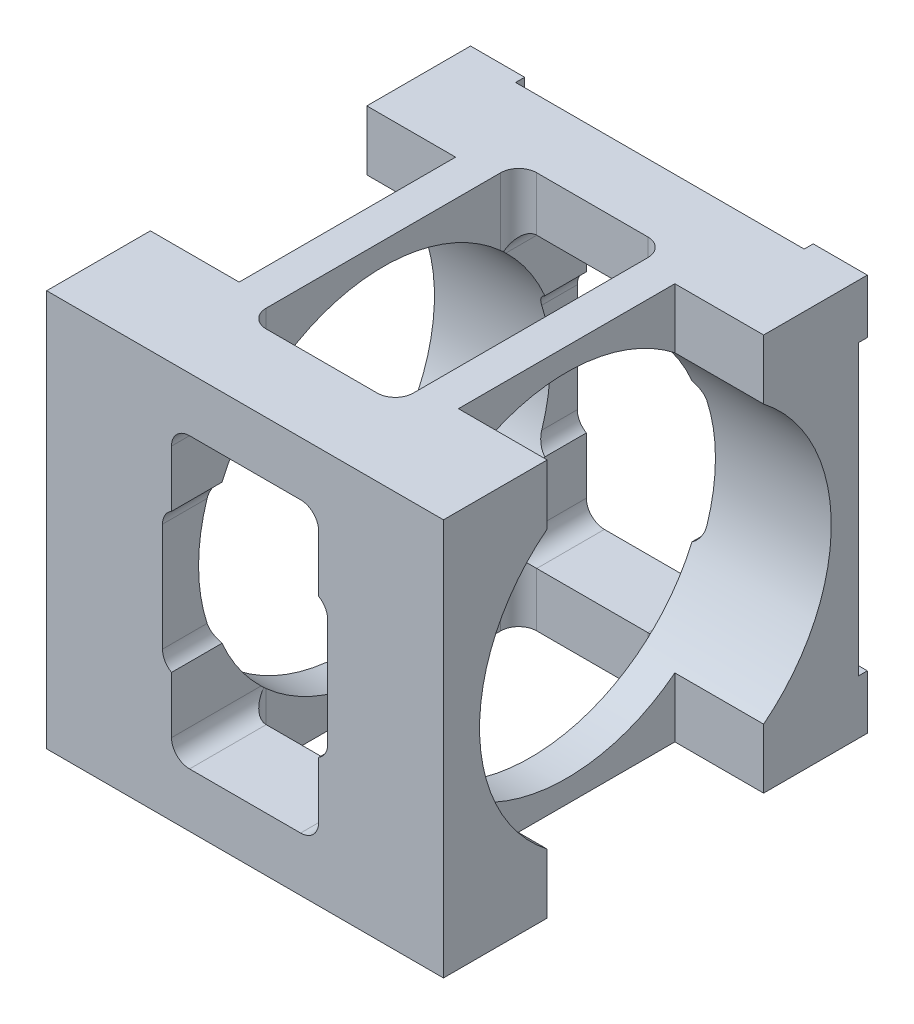
SolidWorks part; units mm, degrees
material "1060 Alloy"
ref_plane "Front Plane" through (0, 0, 0) normal (0, 0, 1) x (1, 0, 0)
ref_plane "Top Plane" through (0, 0, 0) normal (0, 1, 0) x (1, 0, 0)
ref_plane "Right Plane" through (0, 0, 0) normal (1, 0, 0) x (0, 0, -1)
sketch "Sketch1" plane through (0, 0, 0) normal (0, 0, 1) x (1, 0, 0)
  line L0 (0, 70) -> (0, 0) construction
  line L1 (12.5, 70) -> (-12.5, 70) construction
  line L2 (-12.5, 70) -> (-12.5, 0) construction
  line L3 (-11, 40) -> (11, 40)
  line L4 (-11, 40) -> (-11, 62)
  line L5 (-11, 62) -> (11, 62)
  line L6 (11, 40) -> (11, 62)
  line L7 (-11, 40) -> (11, 62) construction
  line L8 (-11, 62) -> (11, 40) construction
  point P5 (0, 51)
  dimension "D1" = 1.5
  dimension "D2" = 8
extrude "Boss-Extrude1" add sketch "Sketch1" along normal offset from surface (23.5 mm away) 1.5
sketch "Sketch2" plane through (11, 0, 0) normal (1, 0, 0) x (0, 0, -1)
  line L1 (-23.5, 51) -> (0, 51) construction
  line L2 (-23.5, 62) -> (-23.5, 40) construction
  line L3 (0, 40) -> (0, 62) construction
  circle A0 centre (-11.75, 51) radius 9.75
  dimension "D1" = 19.5
extrude "Cut-Extrude1" cut sketch "Sketch2" against normal up to next
sketch "Sketch3" plane through (0, 0, 0) normal (0, 0, -1) x (-1, 0, 0)
  line L0 (0, 62) -> (0, 40) construction
  line L1 (-11, 62) -> (11, 62) construction
  line L2 (11, 40) -> (-11, 40) construction
  line L3 (-11, 51) -> (11, 51) construction
  line L4 (-11, 40) -> (-11, 62) construction
  line L5 (11, 62) -> (11, 40) construction
  line L6 (11, 59) -> (8, 59)
  line L7 (-11, 62) -> (-8, 62)
  line L8 (-11, 62) -> (-11, 59)
  line L9 (-11, 59) -> (-8, 59)
  line L10 (-8, 62) -> (-8, 59)
  line L11 (8, 62) -> (8, 59)
  line L12 (11, 62) -> (8, 62)
  line L13 (11, 62) -> (11, 59)
  line L14 (11, 40) -> (11, 43)
  line L15 (11, 40) -> (8, 40)
  line L16 (8, 40) -> (8, 43)
  line L17 (-8, 40) -> (-8, 43)
  line L18 (-11, 43) -> (-8, 43)
  line L19 (-11, 40) -> (-11, 43)
  line L20 (-11, 40) -> (-8, 40)
  line L21 (11, 43) -> (8, 43)
  line M1 (-11, 62) -> (-11, 40)
  line M2 (-11, 40) -> (11, 40)
  line M3 (11, 40) -> (11, 62)
  line M4 (11, 62) -> (-11, 62)
  dimension "D1" = 3
extrude "Cut-Extrude2" cut sketch "Sketch3" against normal blind 0.5 contours L21 L6 L11 L10 L9 L18 L17 L16 M3 M4 M1 M2
sketch3d "3DSketch1"
  line L0 (-11, 51, 23.5) -> (11, 51, 23.5) construction
  line L4 (-11, 40, 23.5) -> (-11, 62, 23.5) construction
  line L5 (11, 62, 23.5) -> (11, 40, 23.5) construction
  line L6 (0, 51, 23.5) -> (0, 51, 0.5) construction
  point P0 (0, 51, 23.5)
sketch "Sketch5" plane through (0, 0, 23.5) normal (0, 0, 1) x (1, 0, 0)
  line L0 (0, 40) -> (0, 62) construction
  line L1 (11, 40) -> (-11, 40) construction
  line L2 (-11, 62) -> (11, 62) construction
  line L3 (3.8786, 43.5) -> (3.8786, 58.5) construction
  line L4 (-4.0786, 43) -> (4.0786, 43)
  line L5 (-4.0786, 43) -> (-4.0786, 59)
  line L6 (-4.0786, 59) -> (4.0786, 59)
  line L7 (4.0786, 43) -> (4.0786, 59)
  line L8 (-4.0786, 43) -> (4.0786, 59) construction
  line L9 (-4.0786, 59) -> (4.0786, 43) construction
  point P6 (0, 51)
  dimension "D1" = 3
  dimension "D2" = 0.2
extrude "Cut-Extrude3" cut sketch "Sketch5" against normal through all
sketch "Sketch6" plane through (0, 62, 0) normal (0, 1, 0) x (1, 0, 0)
  line L0 (3.8786, -19.25) -> (5.815, -19.25) construction
  line L1 (-4.0786, -19.25) -> (4.0786, -19.25)
  line L2 (-4.0786, -19.25) -> (-4.0786, -4.25)
  line L3 (-4.0786, -4.25) -> (4.0786, -4.25)
  line L4 (4.0786, -19.25) -> (4.0786, -4.25)
  line L5 (-4.0786, -19.25) -> (4.0786, -4.25) construction
  line L6 (-4.0786, -4.25) -> (4.0786, -19.25) construction
  line L7 (4.0786, -17.3234) -> (4.0786, -23.5) construction
  point P0 (0, -11.75)
extrude "Cut-Extrude4" cut sketch "Sketch6" against normal through all
sketch "Sketch7" plane through (0, 62, 0) normal (0, 1, 0) x (1, 0, 0)
  line L0 (0, -23.5) -> (0, -0.5) construction
  line L1 (-11, -23.5) -> (11, -23.5) construction
  line L2 (11, -11.75) -> (-11.0546, -11.75) construction
  line L3 (11, -23.5) -> (11, 0) construction
  line L4 (22.5677, -11.75) -> (-56.1439, -11.75) construction
  line L5 (4.0786, -19.25) -> (4.0786, -4.25) construction
  line L6 (6.0786, -17.75) -> (11, -17.75)
  line L7 (6.0786, -17.75) -> (6.0786, -5.75)
  line L8 (6.0786, -5.75) -> (11, -5.75)
  line L9 (11, -17.75) -> (11, -5.75)
  line L10 (6.0786, -17.75) -> (11, -5.75) construction
  line L11 (6.0786, -5.75) -> (11, -17.75) construction
  line L12 (-6.0786, -5.75) -> (-11, -17.75) construction
  line L13 (-6.0786, -17.75) -> (-11, -5.75) construction
  line L14 (-11, -17.75) -> (-11, -5.75)
  line L15 (-6.0786, -5.75) -> (-11, -5.75)
  line L16 (-6.0786, -17.75) -> (-6.0786, -5.75)
  line L17 (-6.0786, -17.75) -> (-11, -17.75)
  point P11 (8.5393, -11.75)
  point P22 (-8.5393, -11.75)
  dimension "D1" = 2
  dimension "D2" = 12
extrude "Cut-Extrude5" cut sketch "Sketch7" against normal through all
sketch "Sketch8" plane through (0, 0, 23.5) normal (0, 0, 1) x (1, 0, 0)
  line L0 (4.0786, 43) -> (4.0786, 59) construction
  line L1 (-3.5786, 47) -> (3.5786, 47)
  line L2 (-4.5786, 48) -> (-4.5786, 54)
  line L3 (-3.5786, 55) -> (3.5786, 55)
  line L4 (4.5786, 48) -> (4.5786, 54)
  line L5 (-4.5786, 47) -> (4.5786, 55) construction
  line L6 (-4.5786, 55) -> (4.5786, 47) construction
  arc A0 (-3.5786, 47) -> (-4.5786, 48) centre (-3.5786, 48) cw
  arc A1 (-4.5786, 54) -> (-3.5786, 55) centre (-3.5786, 54) cw
  arc A2 (3.5786, 55) -> (4.5786, 54) centre (3.5786, 54) cw
  arc A3 (3.5786, 47) -> (4.5786, 48) centre (3.5786, 48) ccw
  point P0 (0, 51)
  dimension "D3" = 1
  dimension "D1" = 8
  dimension "D2" = 0.5
extrude "Cut-Extrude6" cut sketch "Sketch8" against normal through all
fillet "Fillet1" radius 1 16 edges at (4.0786, 59, 2.375) (4.0786, 43, 2.375) (-4.0786, 43, 2.375) (-4.0786, 59, 2.375) (4.0786, 59, 21.375) (-4.0786, 59, 21.375) (-4.0786, 43, 21.375) (4.0786, 43, 21.375) (-4.0786, 60.5, 4.25) (-4.0786, 41.5, 4.25) (4.0786, 41.5, 4.25) (4.0786, 60.5, 4.25) (4.0786, 41.5, 19.25) (4.0786, 60.5, 19.25) (-4.0786, 60.5, 19.25) (-4.0786, 41.5, 19.25)
